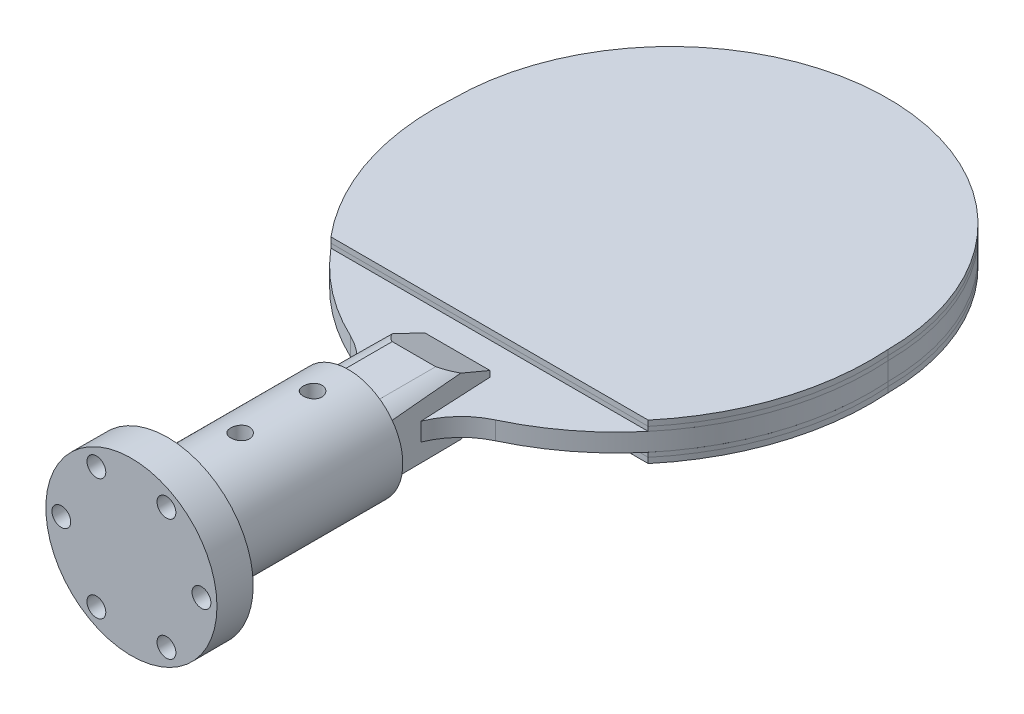
SolidWorks part; units mm, degrees
material "Beech"
ref_plane "Front Plane" through (0, 0, 0) normal (0, 0, 1) x (1, 0, 0)
ref_plane "Top Plane" through (0, 0, 0) normal (0, 1, 0) x (1, 0, 0)
ref_plane "Right Plane" through (0, 0, 0) normal (1, 0, 0) x (0, 0, -1)
sketch "Sketch2" plane through (0, 0, 0) normal (0, 1, 0) x (1, 0, 0)
  line L0 (0, -1000) -> (0, 49000) construction
  line L1 (-12.7, -100.1709) -> (-16.3767, -173.7041)
  line L2 (-13.8398, -176.3709) -> (13.8398, -176.3709)
  line L3 (12.7, -100.1709) -> (16.3767, -173.7041)
  arc A0 (-76.2, 0) -> (76.2, 0) centre (0, 0) cw
  arc A1 (76.2, 0) -> (25.4, -86.7792) centre (-12.4729, -6.35) cw
  arc A2 (-76.2, 0) -> (-25.4, -86.7792) centre (12.4729, -6.35) ccw
  arc A3 (25.4, -86.7792) -> (12.7, -100.1709) centre (36.2208, -109.7589) ccw
  arc A4 (-25.4, -86.7792) -> (-12.7, -100.1709) centre (-36.2208, -109.7589) cw
  arc A5 (-16.3767, -173.7041) -> (-13.8398, -176.3709) centre (-13.8398, -173.8309) ccw
  arc A6 (16.3767, -173.7041) -> (13.8398, -176.3709) centre (13.8398, -173.8309) cw
  point P17 (0, -176.3709)
  point P19 (-16.51, -176.3709)
  point P22 (16.51, -176.3709)
  dimension "D1" = 76.2
  dimension "D3" = 88.9
  dimension "D6" = 25.4
  dimension "D9" = 2.54
  dimension "D2" = 50.8
  dimension "D4" = 6.35
  dimension "D5" = 25.4
  dimension "D7" = 76.2
  dimension "D8" = 16.51
extrude "Boss-Extrude1" add sketch "Sketch2" along normal blind 6.35
sketch "Sketch3" plane through (0, 6.35, 0) normal (0, 1, 0) x (1, 0, 0)
  line L0 (-55.6232, -63.5) -> (55.6232, -63.5)
  arc A0 (76.2, 0) -> (-76.2, 0) centre (0, 0) ccw construction
  arc A1 (-76.2, 0) -> (-25.4, -86.7792) centre (12.4729, -6.35) ccw construction
  arc A2 (25.4, -86.7792) -> (76.2, 0) centre (-12.4729, -6.35) ccw construction
  arc A3 (76.2, 0) -> (-76.2, 0) centre (0, 0) ccw
  arc A4 (-76.2, 0) -> (-55.6232, -63.5) centre (12.4729, -6.35) ccw
  arc A5 (55.6232, -63.5) -> (76.2, 0) centre (-12.4729, -6.35) ccw
  dimension "D1" = 63.5
extrude "Boss-Extrude2" add sketch "Sketch3" along normal blind 1.524 separate body
sketch "Sketch4" plane through (0, 7.874, 0) normal (0, 1, 0) x (1, 0, 0)
  line L0 (-55.6232, -63.5) -> (55.6232, -63.5) construction
  line L1 (-55.6232, -63.5) -> (55.6232, -63.5)
  arc A0 (-76.2, 0) -> (-55.6232, -63.5) centre (12.4729, -6.35) ccw construction
  arc A1 (76.2, 0) -> (-76.2, 0) centre (0, 0) ccw construction
  arc A2 (55.6232, -63.5) -> (76.2, 0) centre (-12.4729, -6.35) ccw construction
  arc A3 (-76.2, 0) -> (-55.6232, -63.5) centre (12.4729, -6.35) ccw
  arc A4 (76.2, 0) -> (-76.2, 0) centre (0, 0) ccw
  arc A5 (55.6232, -63.5) -> (76.2, 0) centre (-12.4729, -6.35) ccw
extrude "Boss-Extrude4" add sketch "Sketch4" along normal blind 1.905 separate body
ref_plane "Plane1" through (0, 3.175, 0) normal (0, 1, 0) x (1, 0, 0)
sketch "Sketch5" plane through (0, 0, 0) normal (0, -1, 0) x (1, 0, 0)
  line L0 (55.6232, 63.5) -> (-55.6232, 63.5)
  line L3 (12.7, 100.1709) -> (16.3767, 173.7041)
  line L4 (13.8398, 176.3709) -> (-13.8398, 176.3709)
  line L5 (-16.3767, 173.7041) -> (-12.7, 100.1709)
  arc A7 (-25.4, 86.7792) -> (-76.2, 0) centre (12.4729, 6.35) ccw
  arc A8 (-76.2, 0) -> (76.2, 0) centre (0, 0) ccw
  arc A9 (76.2, 0) -> (25.4, 86.7792) centre (-12.4729, 6.35) ccw
  arc A10 (12.7, 100.1709) -> (25.4, 86.7792) centre (36.2208, 109.7589) ccw
  arc A11 (16.3767, 173.7041) -> (13.8398, 176.3709) centre (13.8398, 173.8309) ccw
  arc A12 (-13.8398, 176.3709) -> (-16.3767, 173.7041) centre (-13.8398, 173.8309) ccw
  arc A13 (-25.4, 86.7792) -> (-12.7, 100.1709) centre (-36.2208, 109.7589) ccw
  arc A14 (-55.6232, 63.5) -> (-76.2, 0) centre (12.4729, 6.35) ccw
  arc A15 (-76.2, 0) -> (76.2, 0) centre (0, 0) ccw
  arc A16 (76.2, 0) -> (55.6232, 63.5) centre (-12.4729, 6.35) ccw
  dimension "D2" = 63.5
  dimension "D1" = 0
extrude "Boss-Extrude5" add sketch "Sketch5" along normal blind 1.524 separate body
sketch "Sketch6" plane through (0, -1.524, 0) normal (0, -1, 0) x (1, 0, 0)
  line L1 (55.6232, 63.5) -> (-55.6232, 63.5)
  line L2 (55.6232, 63.5) -> (-55.6232, 63.5)
  arc A3 (76.2, 0) -> (55.6232, 63.5) centre (-12.4729, 6.35) ccw
  arc A4 (-55.6232, 63.5) -> (-76.2, 0) centre (12.4729, 6.35) ccw
  arc A5 (-76.2, 0) -> (76.2, 0) centre (0, 0) ccw
  arc A6 (76.2, 0) -> (55.6232, 63.5) centre (-12.4729, 6.35) ccw
  arc A7 (-55.6232, 63.5) -> (-76.2, 0) centre (12.4729, 6.35) ccw
  arc A8 (-76.2, 0) -> (76.2, 0) centre (0, 0) ccw
  dimension "D1" = 0
extrude "Boss-Extrude6" add sketch "Sketch6" along normal blind 1.905 separate body
sketch "Sketch7" plane through (0, 6.35, 0) normal (0, 1, 0) x (1, 0, 0)
  line L0 (-12.7, -100.1709) -> (-16.3767, -173.7041) construction
  line L1 (16.3767, -173.7041) -> (12.7, -100.1709) construction
  line L2 (-13.8398, -176.3709) -> (13.8398, -176.3709) construction
  line L3 (-11.43, -74.7709) -> (-16.3767, -173.7041)
  line L4 (16.3767, -173.7041) -> (11.43, -74.7709)
  line L5 (-13.8398, -176.3709) -> (13.8398, -176.3709)
  line L6 (-11.43, -74.7709) -> (11.43, -74.7709)
  arc A0 (13.8398, -176.3709) -> (16.3767, -173.7041) centre (13.8398, -173.8309) ccw construction
  arc A1 (-16.3767, -173.7041) -> (-13.8398, -176.3709) centre (-13.8398, -173.8309) ccw construction
  arc A2 (13.8398, -176.3709) -> (16.3767, -173.7041) centre (13.8398, -173.8309) ccw
  arc A3 (-16.3767, -173.7041) -> (-13.8398, -176.3709) centre (-13.8398, -173.8309) ccw
  dimension "D1" = 101.6
extrude "Boss-Extrude7" add sketch "Sketch7" along normal blind 8.89
sketch "Sketch8" plane through (0, 0, 176.3709) normal (0, 0, 1) x (1, 0, 0)
  line L0 (-16.3798, 15.24) -> (-16.3798, 0) construction
  line L1 (-13.8398, 15.24) -> (13.8398, 15.24) construction
  line L2 (16.3798, 0) -> (16.3798, 15.24) construction
  line L4 (0, -1000) -> (0, 15.24) construction
  line L5 (16.3798, 15.24) -> (13.8398, 15.24) construction
  line L6 (-13.8398, 15.24) -> (-16.3798, 15.24) construction
  line L7 (-13.8398, 15.24) -> (-7.62, 15.24)
  line L8 (16.3798, 15.24) -> (13.8398, 15.24)
  line L9 (16.3798, 7.62) -> (16.3798, 15.24)
  line L10 (-13.8398, 15.24) -> (-16.3798, 15.24)
  line L11 (-16.3798, 15.24) -> (-16.3798, 7.62)
  line L12 (7.62, 15.24) -> (13.8398, 15.24)
  arc A0 (-16.3798, 7.62) -> (-7.62, 15.24) centre (-4.5865, 2.9076) cw
  arc A1 (16.3798, 7.62) -> (7.62, 15.24) centre (4.5865, 2.9076) ccw
  dimension "D2" = 12.7
  dimension "D3" = 12.7
  dimension "D1" = 15.24
extrude "Cut-Extrude1" cut sketch "Sketch8" against normal blind 101.6
sketch "Sketch9" plane through (0, 0, -0.1919) normal (1, 0, 0) x (0, 0, -1)
  line L0 (-74.9628, 8.382) -> (-90.2028, 15.24)
  line L1 (-74.9628, 13.606) -> (-74.9628, 6.35) construction
  line L2 (-74.9628, 15.24) -> (-176.5628, 15.24) construction
  line L3 (-90.2028, 15.24) -> (-74.9628, 15.24)
  line L4 (-74.9628, 15.24) -> (-74.9628, 8.382)
  dimension "D1" = 15.24
  dimension "D2" = 15.24
  dimension "D3" = 6.858
extrude "Cut-Extrude2" cut sketch "Sketch9" against normal mid plane 50.8
mirror "Mirror8" about plane through (0, 3.175, 0) normal (0, 1, 0) of "Cut-Extrude2", "Cut-Extrude1", "Boss-Extrude7"
sketch "Sketch10" plane through (0, 0, 176.3709) normal (0, 0, 1) x (1, 0, 0)
  line L0 (0, 15.24) -> (0, -8.89) construction
  line L1 (-7.62, 15.24) -> (7.62, 15.24) construction
  line L2 (-7.62, -8.89) -> (7.62, -8.89) construction
  line L3 (-16.3798, 3.175) -> (16.3798, 3.175) construction
  line L4 (-16.3798, 7.6201) -> (-16.3798, -1.2701) construction
  line L5 (16.3798, -1.27) -> (16.3798, 7.62) construction
  circle A1 centre (0, 3.175) radius 30
  dimension "D1" = 60
extrude "Boss-Extrude8" add sketch "Sketch10" along normal blind 12.7 and the other way blind 63.5
sketch "Sketch11" plane through (0, 0, 0) normal (0, 1, 0) x (1, 0, 0)
  line L0 (30, -112.8709) -> (-30, -112.8709) construction
  circle A0 centre (0, -125.5709) radius 3.302
  circle A1 centre (0, -150.9709) radius 3.302
  dimension "D1" = 6.604
  dimension "D2" = 25.4
  dimension "D3" = 12.7
extrude "Cut-Extrude3" cut sketch "Sketch11" against normal through all both and the other way through all
sketch "Sketch12" plane through (0, 0, 112.8709) normal (0, 0, -1) x (-1, 0, 0)
  circle A0 centre (0.0907, 2.8996) radius 24.7101 construction
  circle A1 centre (0.0907, 2.8996) radius 37.4101
  circle A2 centre (0.0907, 2.8996) radius 19.05
  dimension "D2" = 38.1
  dimension "D1" = 12.7
extrude "Cut-Extrude4" cut sketch "Sketch12" against normal blind 63.5
sketch "Sketch13" plane through (0, 0, 176.3709) normal (0, 0, -1) x (-1, 0, 0)
  line L0 (0, 33.175) -> (0, -26.825) construction
  line L1 (-30, 3.175) -> (-18.9573, 3.175) construction
  line L2 (19.1388, 3.175) -> (30, 3.175) construction
  circle A0 centre (0, 3.175) radius 30 construction
  circle A1 centre (0, 3.175) radius 30 construction
  circle A2 centre (0.0907, 2.8996) radius 19.05 construction
  circle A3 centre (0.0907, 2.8996) radius 19.05 construction
  circle A4 centre (24.5694, 3.175) radius 3.302
  dimension "D1" = 6.604
extrude "Cut-Extrude6" cut sketch "Sketch13" against normal through all
ref_axis "Axis1" through (0, 3.175, 176.3709) along (0, 0, 1)
pattern_circular "CirPattern1" count 6 over 360 about axis through (0, 3.175, 176.3709) along (0, 0, 1) of "Cut-Extrude6"
